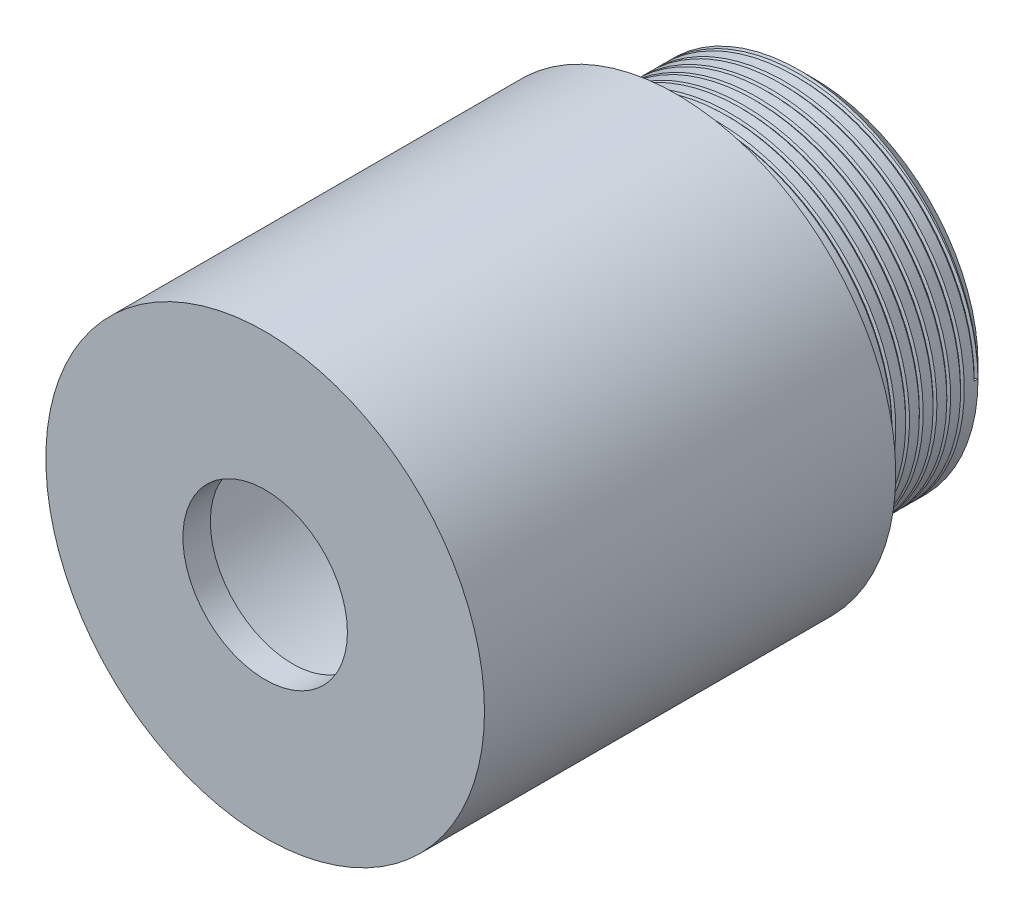
SolidWorks part; units mm, degrees
ref_plane "Ön Düzlem" through (0, 0, 0) normal (0, 0, 1) x (1, 0, 0)
ref_plane "Üst Düzlem" through (0, 0, 0) normal (0, 1, 0) x (1, 0, 0)
ref_plane "Sağ Düzlem" through (0, 0, 0) normal (1, 0, 0) x (0, 0, -1)
sketch "Çizim1" plane through (0, 0, 0) normal (0, 0, 1) x (1, 0, 0)
  circle A0 centre (0, 0) radius 13
  dimension "D1" = 26
extrude "Yükseklik-Ekstrüzyon1" add sketch "Çizim1" along normal blind 10
sketch "Çizim2" plane through (0, 0, 10) normal (0, 0, 1) x (1, 0, 0)
  circle A0 centre (0, 0) radius 16
  dimension "D1" = 32
extrude "Yükseklik-Ekstrüzyon2" add sketch "Çizim2" along normal blind 30
sketch "Çizim3" plane through (0, 0, 0) normal (0, 0, -1) x (-1, 0, 0)
  circle A0 centre (0, 0) radius 11
  circle A2 centre (0, 0) radius 13 construction
  dimension "D1" = 2
extrude "Kes-Ekstrüzyon1" cut sketch "Çizim3" against normal blind 38
sketch "Çizim4" plane through (0, 0, 40) normal (0, 0, 1) x (1, 0, 0)
  circle A0 centre (0, 0) radius 6
  dimension "D1" = 12
extrude "Kes-Ekstrüzyon2" cut sketch "Çizim4" against normal blind 38
chamfer "Pah1" distance 1 angle 45 1 edges at (13, 0, 0)
thread "Diş1" pitch 0.3175 method cut profile "Diş Profili1" start angle 0, offset 0, length 10, pitch 1, diameter 26
ref_plane "Düzlem1" through (13, 0, 1) normal (0, -1, 0) x (1, 0, 0)
sketch "Diş Profili1" plane through (13, 0, 1) normal (0, -1, 0) x (1, 0, 0)
  line L0 (0, 0) -> (0, 0.3175) construction
  line L11 (0, 0) -> (0, 0.2778)
  line L12 (0, 0.2778) -> (-0.1719, 0.1786)
  line L13 (-0.1719, 0.1786) -> (-0.1719, 0.0992)
  line L15 (-0.1719, 0.0992) -> (0, 0)
  line L17 (-0.1719, 0.1389) -> (0, 0.1389) construction
  point P2 (0, 0)
  dimension "Pitch" = 0.3175
  dimension "Profile_Angle" = 60
  dimension "Profile_Land" = 0.0794
  dimension "Profile_Height" = 0.1719
